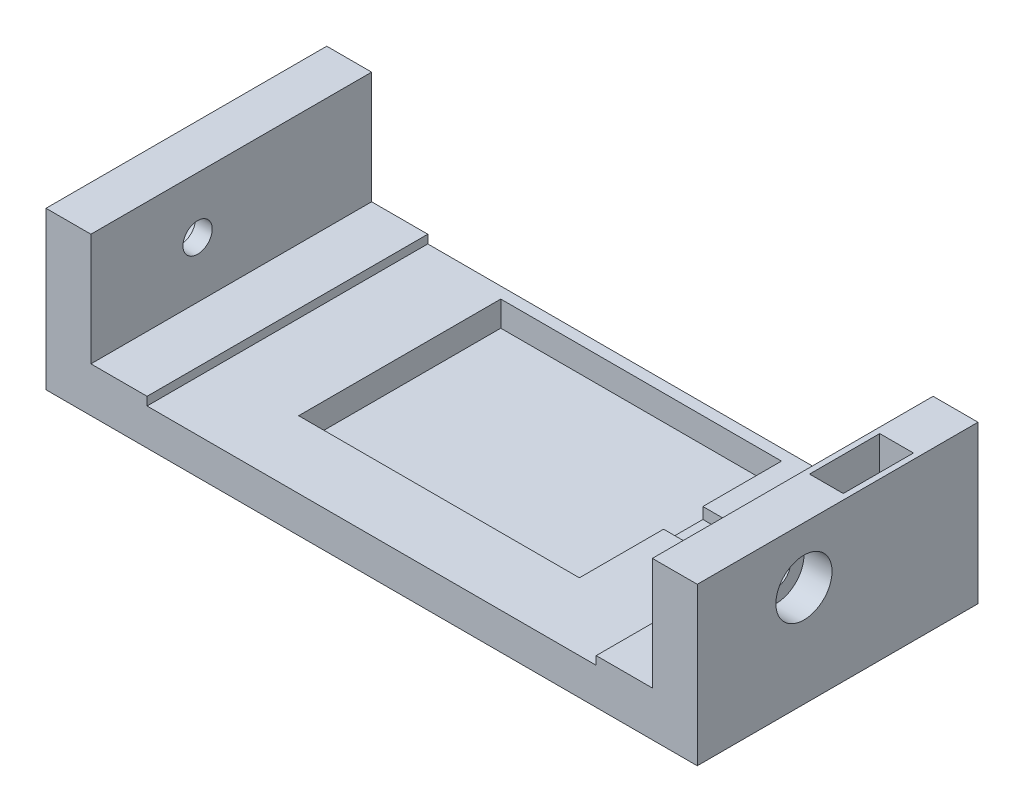
SolidWorks part; units mm, degrees
ref_plane "前视基准面" through (0, 0, 0) normal (0, 0, 1) x (1, 0, 0)
ref_plane "上视基准面" through (0, 0, 0) normal (0, 1, 0) x (1, 0, 0)
ref_plane "右视基准面" through (0, 0, 0) normal (1, 0, 0) x (0, 0, -1)
other "Configuration Table"
sketch "草图1" plane through (0, 0, 0) normal (0, 1, 0) x (1, 0, 0)
  line L0 (50, 25) -> (50, -25)
  line L3 (-50, 25) -> (-50, -25)
  line L6 (50, -25) -> (-50, -25)
  line L9 (-50, 25) -> (50, 25)
extrude "凸台-拉伸1" add sketch "草图1" along normal blind 2 contours L3 L6 L0 L9
sketch "草图2" plane through (0, 2, 0) normal (0, 1, 0) x (1, 0, 0)
  line L2 (0, 23) -> (25, 23)
  line L3 (25, 23) -> (25, -13)
  line L4 (0, 23) -> (-25, 23)
  line L5 (-25, 23) -> (-25, -13)
  line L6 (-25, -13) -> (25, -13)
  line L7 (-50, -25) -> (50, -25)
  line L8 (-50, -25) -> (-50, 25)
  line L9 (-50, 25) -> (50, 25)
  line L10 (50, -25) -> (50, 25)
extrude "凸台-拉伸2" add sketch "草图2" along normal blind 5 contours L8 L7 L10 L9 | L4 L5 L6 L3 L2
sketch "草图4" plane through (0, 0, 0) normal (0, -1, 0) x (1, 0, 0)
  text T0 "RFID\r\n" font "宋体" height in points 42
extrude "切除-拉伸1" cut sketch "草图4" against normal blind 1
sketch "草图5" plane through (0, 7, 0) normal (0, 1, 0) x (1, 0, 0)
  line L0 (25, -13) -> (25, 9)
  line L1 (25, 23) -> (25, -13) construction
  line L2 (25, 9) -> (50, 9)
  line L3 (50, -25) -> (50, 25) construction
  line L4 (50, 9) -> (50, 2)
  line L5 (50, 2) -> (25, 2)
  line L6 (25, 2) -> (25, 9)
  line M6 (50, -25) -> (50, 25)
  line M9 (25, 23) -> (25, -13)
extrude "切除-拉伸2" cut sketch "草图5" against normal blind 2.5 contours L5 L2 M6 M9 region at (37.5, 7, -5.5)
sketch "草图7" plane through (0, 7, 0) normal (0, 1, 0) x (1, 0, 0)
  line L0 (-50, -25) -> (50, -25) construction
  line L1 (50, 25) -> (40, 25)
  line L2 (50, 25) -> (50, -25)
  line L3 (50, -25) -> (40, -25)
  line L4 (40, 25) -> (40, -25)
  line L6 (-50, 25) -> (-40, 25)
  line L7 (-50, 25) -> (-50, -25)
  line L8 (-50, -25) -> (-40, -25)
  line L9 (-40, 25) -> (-40, -25)
extrude "凸台-拉伸3" add sketch "草图7" along normal blind 1
sketch "草图8" plane through (0, 7, 0) normal (0, 1, 0) x (1, 0, 0)
  line L1 (-40, 25) -> (40, 25)
  line L2 (-40, 25) -> (-40, -25)
  line L3 (-40, -25) -> (40, -25)
  line L4 (40, 25) -> (40, -25)
extrude "切除-拉伸3" cut sketch "草图8" against normal blind 0.5
sketch "草图9" plane through (0, 0, 0) normal (0, -1, 0) x (1, 0, 0)
  line L1 (50, 25) -> (58, 25)
  line L2 (50, 25) -> (50, -25)
  line L3 (50, -25) -> (58, -25)
  line L4 (58, 25) -> (58, -25)
extrude "凸台-拉伸4" add sketch "草图9" against normal blind 4.5
sketch "草图10" plane through (0, 4.5, 0) normal (0, 1, 0) x (1, 0, 0)
  line L0 (25, 2) -> (50, 2)
  line L1 (50, 2) -> (58, 2)
  line L2 (58, 25) -> (58, -25) construction
  line L3 (58, 2) -> (58, -25)
  line L4 (58, -25) -> (50, -25)
  line L5 (50, -25) -> (50, 2)
  line M6 (50, 2) -> (50, -25)
  line M7 (50, -25) -> (58, -25)
  line M8 (58, -25) -> (58, 25)
extrude "凸台-拉伸5" add sketch "草图10" along normal blind 23.5 contours L1 M6 M7 M8 region at (54, 4.5, 11.5)
sketch "草图11" plane through (50, 0, 0) normal (-1, 0, 0) x (0, 0, 1)
  line L0 (-2, 8) -> (6, 8)
  line L1 (25, 8) -> (-2, 8) construction
  line L2 (6, 8) -> (6, 18)
  circle A0 centre (6, 18) radius 2.6
extrude "切除-拉伸4" cut sketch "草图11" against normal blind 23.5 contours A0 region at (50, 16.2135, 7.7865)
sketch "草图12" plane through (58, 0, 0) normal (1, 0, 0) x (0, 0, -1)
  circle A0 centre (-6, 18) radius 5
extrude "切除-拉伸5" cut sketch "草图12" against normal blind 5
sketch "草图13" plane through (0, 0, 0) normal (0, -1, 0) x (1, 0, 0)
  line L1 (-50, 25) -> (-58, 25)
  line L2 (-50, 25) -> (-50, -25)
  line L3 (-50, -25) -> (-58, -25)
  line L4 (-58, 25) -> (-58, -25)
extrude "凸台-拉伸6" add sketch "草图13" against normal blind 28
sketch "草图14" plane through (53, 0, 0) normal (1, 0, 0) x (0, 0, -1)
  circle A0 centre (-6, 18) radius 2.6
extrude "切除-拉伸6" cut sketch "草图14" against normal blind 3000
sketch "草图15" plane through (-58, 0, 0) normal (-1, 0, 0) x (0, 0, 1)
  circle A0 centre (6, 18) radius 5
extrude "切除-拉伸7" cut sketch "草图15" against normal blind 5
sketch "草图16" plane through (0, 4.5, 0) normal (0, 1, 0) x (1, 0, 0)
  line L0 (50, 25) -> (58, 25)
  line L1 (50, 2) -> (58, 2) construction
  line L2 (58, 25) -> (58, 2)
  line L3 (58, 2) -> (57, 2)
  line L4 (51, 2) -> (50, 2)
  line L5 (54, 14.5) -> (57, 14.5)
  line L6 (57, 14.5) -> (57, 2)
  line L7 (57, 2) -> (51, 2)
  line L8 (51, 2) -> (51, 14.5)
  line L9 (51, 14.5) -> (54, 14.5)
  line L10 (51, 14.5) -> (50, 14.5)
  line L11 (50, 2) -> (50, 25) construction
  line L12 (50, 14.5) -> (50, 25)
  line M10 (25, 2) -> (58, 2)
  line M11 (58, 2) -> (58, 25)
  line M12 (58, 25) -> (50, 25)
  line M13 (50, 25) -> (50, 9)
extrude "凸台-拉伸8" add sketch "草图16" along normal blind 23.5 contours L10 L9 L5 L6 M10 M11 M12 M13 region at (54.4534, 4.5, -18.2604)
sketch "草图17" plane through (0, 4.5, 0) normal (0, 1, 0) x (1, 0, 0)
  line L0 (50, 2) -> (57, 2) construction
  line L1 (57, 14.5) -> (51, 14.5)
  line L2 (57, 14.5) -> (57, 2)
  line L3 (57, 2) -> (51, 2)
  line L4 (51, 14.5) -> (51, 2)
  line L5 (40, 9) -> (50, 9)
  line L6 (50, 2) -> (50, 14.5) construction
  line L7 (25, 9) -> (50, 9) construction
  line L8 (50, 9) -> (50, 14.5)
  line L9 (50, 14.5) -> (51, 14.5)
  line L10 (50, 9) -> (51, 9)
  line L11 (51, 9) -> (51, 14.5)
  line M5 (57, 14.5) -> (50, 14.5)
  line M6 (50, 14.5) -> (50, 9)
extrude "凸台-拉伸9" add sketch "草图17" along normal blind 23.5 contours L10 L4 M6 M5 region at (50.5, 4.5, -11.75)
sketch "草图18" plane through (0, 28, 0) normal (0, 1, 0) x (1, 0, 0)
  line L0 (50, 2) -> (57, 2) construction
  line L1 (50, 9) -> (51, 9)
  line L2 (50, 9) -> (50, 2)
  line L3 (50, 2) -> (51, 2)
  line L4 (51, 9) -> (51, 2)
extrude "凸台-拉伸10" add sketch "草图18" against normal blind 21.5
sketch "草图19" plane through (0, 4.5, 0) normal (0, 1, 0) x (1, 0, 0)
  line L1 (51, 9) -> (57, 9)
  line L2 (51, 9) -> (51, 14.5)
  line L3 (51, 14.5) -> (57, 14.5)
  line L4 (57, 9) -> (57, 14.5)
extrude "凸台-拉伸11" add sketch "草图19" along normal blind 8
sketch "草图20" plane through (0, 0, 0) normal (0, -1, 0) x (-1, 0, 0)
  line L4 (45.1052, -16.417) -> (43.2259, -15.7329)
  line L6 (37.5877, -13.6808) -> (35.7083, -12.9968)
  line L8 (30.0702, -10.9446) -> (28.1908, -10.2606)
  line L9 (45.1052, 16.417) -> (43.2259, 15.7329)
  line L11 (37.5877, 13.6808) -> (35.7083, 12.9968)
  line L13 (30.0702, 10.9446) -> (28.1908, 10.2606)
  line L14 (-45.1052, -16.417) -> (-43.2259, -15.7329)
  line L16 (-37.5877, -13.6808) -> (-35.7083, -12.9968)
  line L18 (-30.0702, -10.9446) -> (-28.1908, -10.2606)
  line L19 (-45.1052, 16.417) -> (-43.2259, 15.7329)
  line L21 (-37.5877, 13.6808) -> (-35.7083, 12.9968)
  line L23 (-30.0702, 10.9446) -> (-28.1908, 10.2606)
  arc A6 (-45.1052, -16.417) -> (-45.1052, 16.417) centre (0, 0) cw
  arc A7 (45.1052, -16.417) -> (45.1052, 16.417) centre (0, 0) ccw
  arc A8 (43.2259, -15.7329) -> (43.2259, 15.7329) centre (0, 0) ccw
  arc A9 (37.5877, -13.6808) -> (37.5877, 13.6808) centre (0, 0) ccw
  arc A10 (35.7083, -12.9968) -> (35.7083, 12.9968) centre (0, 0) ccw
  arc A11 (30.0702, -10.9446) -> (30.0702, 10.9446) centre (0, 0) ccw
  arc A12 (28.1908, -10.2606) -> (28.1908, 10.2606) centre (0, 0) ccw
  arc A13 (-43.2259, -15.7329) -> (-43.2259, 15.7329) centre (0, 0) cw
  arc A14 (-37.5877, -13.6808) -> (-37.5877, 13.6808) centre (0, 0) cw
  arc A15 (-35.7083, -12.9968) -> (-35.7083, 12.9968) centre (0, 0) cw
  arc A16 (-30.0702, -10.9446) -> (-30.0702, 10.9446) centre (0, 0) cw
  arc A17 (-28.1908, -10.2606) -> (-28.1908, 10.2606) centre (0, 0) cw
extrude "切除-拉伸8" cut sketch "草图20" against normal blind 1
fillet "圆角1" radius 1 12 edges at (-30.0702, 0.5, -10.9446) (-28.1908, 0.5, -10.2606) (-35.7083, 0.5, -12.9968) (-37.5877, 0.5, -13.6808) (-45.1052, 0.5, -16.417) (-43.2259, 0.5, -15.7329) (-30.0702, 0.5, 10.9446) (-28.1908, 0.5, 10.2606) (-35.7083, 0.5, 12.9968) (-37.5877, 0.5, 13.6808) (-43.2259, 0.5, 15.7329) (-45.1052, 0.5, 16.417)
fillet "圆角2" radius 1 12 edges at (45.1052, 0.5, -16.417) (43.2259, 0.5, -15.7329) (35.7083, 0.5, -12.9968) (37.5877, 0.5, -13.6808) (30.0702, 0.5, -10.9446) (28.1908, 0.5, -10.2606) (45.1052, 0.5, 16.417) (43.2259, 0.5, 15.7329) (35.7083, 0.5, 12.9968) (37.5877, 0.5, 13.6808) (30.0702, 0.5, 10.9446) (28.1908, 0.5, 10.2606)
